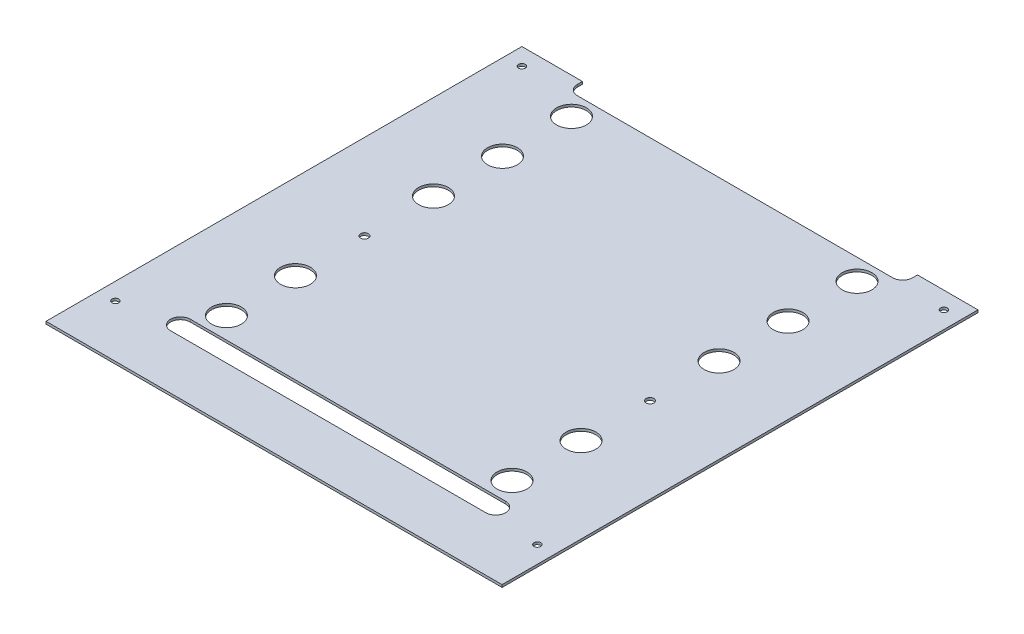
SolidWorks part; units mm, degrees
material "PC High Viscosity"
ref_plane "Front Plane" through (0, 0, 0) normal (0, 0, 1) x (1, 0, 0)
ref_plane "Top Plane" through (0, 0, 0) normal (0, 1, 0) x (1, 0, 0)
ref_plane "Right Plane" through (0, 0, 0) normal (1, 0, 0) x (0, 0, -1)
sketch "Sketch1" plane through (0, 0, 0) normal (0, 1, 0) x (1, 0, 0)
  line L0 (-100.965, -111.379) -> (100.965, -111.379) construction
  line L1 (-146.05, 152.4) -> (146.05, 152.4)
  line L2 (-146.05, 152.4) -> (-146.05, -152.4)
  line L3 (-146.05, -152.4) -> (146.05, -152.4)
  line L4 (146.05, 152.4) -> (146.05, -152.4)
  line L5 (-146.05, 152.4) -> (146.05, -152.4) construction
  line L6 (-146.05, -152.4) -> (146.05, 152.4) construction
  line L7 (-100.965, -105.029) -> (100.965, -105.029)
  line L8 (-100.965, -117.729) -> (100.965, -117.729)
  line L9 (-100.965, 149.225) -> (100.965, 149.225) construction
  line L10 (-100.965, 155.575) -> (100.965, 155.575)
  line L11 (-100.965, 142.875) -> (100.965, 142.875)
  line L12 (-107.315, 149.225) -> (-107.315, 155.575)
  line L13 (-107.315, 155.575) -> (-100.965, 155.575)
  line L14 (107.315, 149.225) -> (107.315, 155.575)
  line L15 (107.315, 155.575) -> (100.965, 155.575)
  line L16 (-135.128, 141.478) -> (135.128, 141.478) construction
  arc A0 (-100.965, -105.029) -> (-100.965, -117.729) centre (-100.965, -111.379) ccw
  arc A1 (100.965, -117.729) -> (100.965, -105.029) centre (100.965, -111.379) ccw
  arc A2 (-100.965, 155.575) -> (-100.965, 142.875) centre (-100.965, 149.225) ccw
  arc A3 (100.965, 142.875) -> (100.965, 155.575) centre (100.965, 149.225) ccw
  circle A4 centre (-135.128, 141.478) radius 2.1527
  circle A5 centre (-135.128, -118.872) radius 2.1527
  circle A6 centre (135.128, 141.478) radius 2.1527
  circle A7 centre (135.128, -118.872) radius 2.1527
  circle A8 centre (-91.44, 129.54) radius 9.525
  circle A9 centre (91.44, 129.54) radius 9.525
  circle A10 centre (91.44, 85.344) radius 9.525
  circle A11 centre (-91.44, 85.344) radius 9.525
  circle A12 centre (91.44, 41.148) radius 9.525
  circle A13 centre (-91.44, 41.148) radius 9.525
  circle A14 centre (91.44, -3.048) radius 9.525 construction
  circle A15 centre (-91.44, -3.048) radius 9.525 construction
  circle A16 centre (91.44, -47.244) radius 9.525
  circle A17 centre (-91.44, -47.244) radius 9.525
  circle A18 centre (91.44, -91.44) radius 9.525
  circle A19 centre (-91.44, -91.44) radius 9.525
  circle A20 centre (-91.44, -3.048) radius 2.4892
  circle A21 centre (91.44, -3.048) radius 2.4892
  point P0 (0, 0)
  point P8 (0, -111.379)
  point P13 (0, -111.379)
  point P14 (0, -152.4)
  point P17 (0, 149.225)
  point P37 (0, 141.478)
  dimension "D4" = 6.35
  dimension "D9" = 4.3053
  dimension "D11" = 19.05
  dimension "D17" = 4.9784
  dimension "D1" = 292.1
  dimension "D2" = 304.8
  dimension "D3" = 45.085
  dimension "D5" = 41.021
  dimension "D6" = 3.175
  dimension "D7" = 10.922
  dimension "D8" = 10.922
  dimension "D10" = 33.528
  dimension "D12" = 54.61
  dimension "D13" = 22.86
  dimension "D14" = 54.61
  dimension "D16" = 44.196
  dimension "D15" = 6
extrude "Boss-Extrude1" add sketch "Sketch1" along normal blind 1.5875 contours A3 L11 A2 L12 L1 L2 L3 L4 L14 A1 L8 A0 L7 region at (0, 0, 0.8236)
